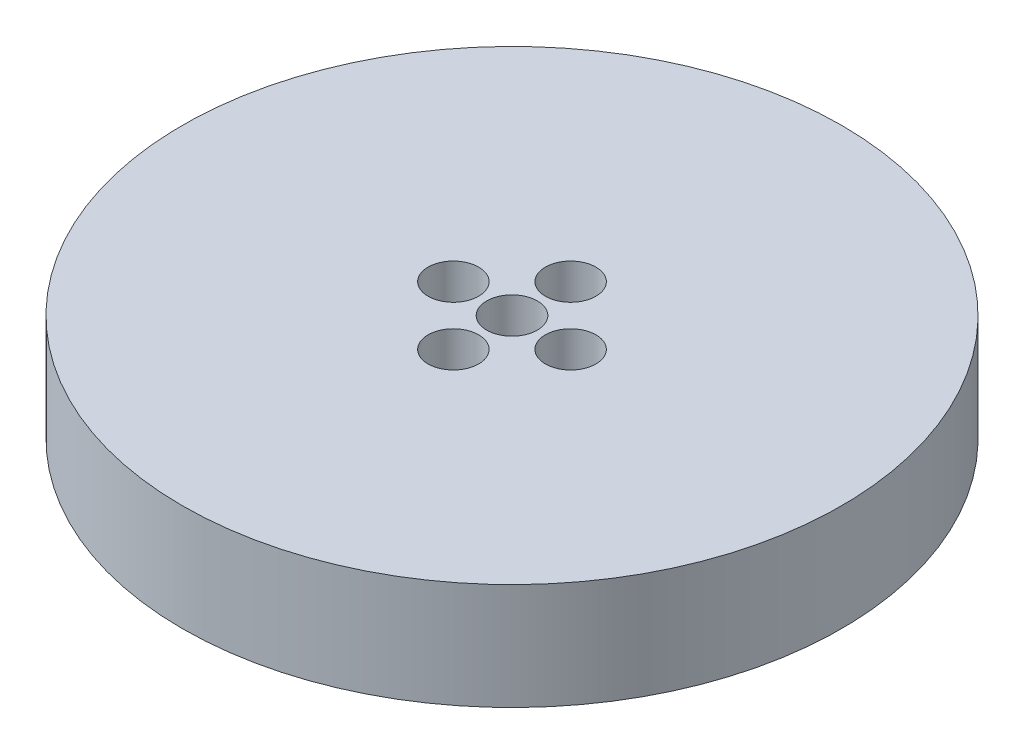
SolidWorks part; units mm, degrees
ref_plane "Front Plane" through (0, 0, 0) normal (0, 0, 1) x (1, 0, 0)
ref_plane "Top Plane" through (0, 0, 0) normal (0, 1, 0) x (1, 0, 0)
ref_plane "Right Plane" through (0, 0, 0) normal (1, 0, 0) x (0, 0, -1)
sketch "Sketch1" plane through (0, 0, 0) normal (0, 1, 0) x (1, 0, 0)
  circle A0 centre (0, 0) radius 65
  dimension "FLANGE_OD" = 130
extrude "Boss-Extrude1" add sketch "Sketch1" along normal blind 21
sketch "Sketch2" plane through (0, 0, 0) normal (0, 1, 0) x (1, 0, 0)
  circle A0 centre (0, 0) radius 5
  dimension "BORE_D" = 10
extrude "Cut-Extrude1" cut sketch "Sketch2" along normal through all
sketch "Sketch3" plane through (0, 21, 0) normal (0, 1, 0) x (1, 0, 0)
  circle A0 centre (0, 0) radius 11.5669 construction
  circle A1 centre (-11.5669, 0) radius 4.9868
  dimension "BOLT_D" = 9.9736
  dimension "BOLT_PCD" = 23.1338
extrude "Cut-Extrude2" cut sketch "Sketch3" against normal blind 18.0064
pattern_circular "CirPattern1" count 4 over 360 about axis through (0, 0, 0) along (0, 1, 0) of "Cut-Extrude2"
